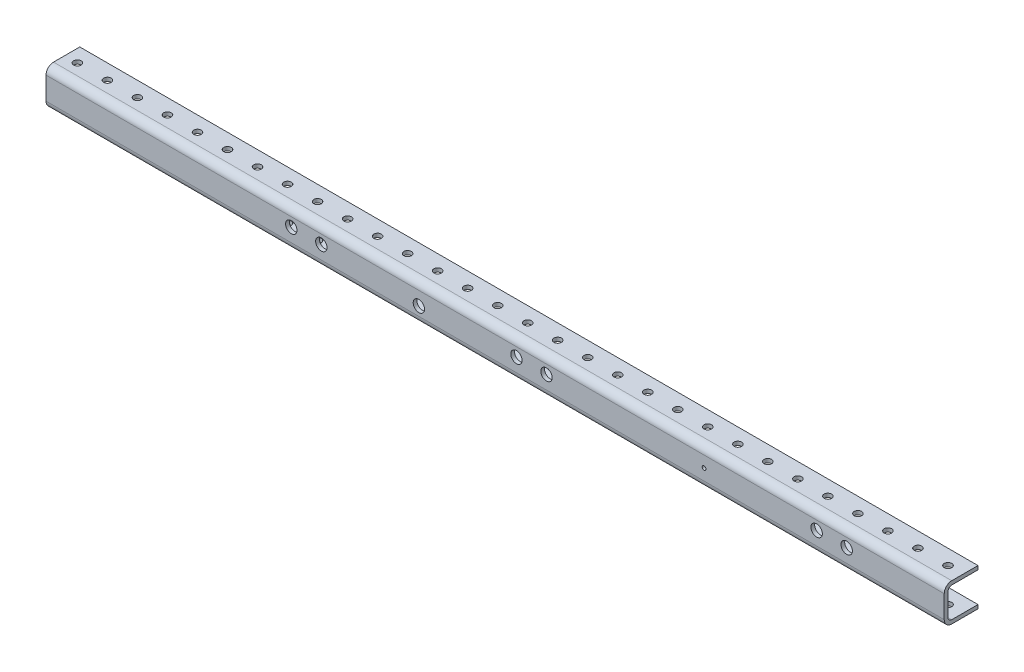
SolidWorks part; units mm, degrees
material "5052-O, Rod (SS)"
ref_plane "Front Plane" through (0, 0, 0) normal (0, 0, 1) x (1, 0, 0)
ref_plane "Top Plane" through (0, 0, 0) normal (0, 1, 0) x (1, 0, 0)
ref_plane "Right Plane" through (0, 0, 0) normal (1, 0, 0) x (0, 0, -1)
ref_plane "Plane1" through (0, 0, 3.175) normal (0, 0, 1) x (1, 0, 0)
sketch "Sketch1" plane through (0, 0, 3.175) normal (0, 0, 1) x (1, 0, 0)
  line L0 (872.98, -7.202) -> (872.98, 24.548)
  line L1 (872.98, 24.548) -> (-16.02, 24.548)
  line L2 (-16.02, 24.548) -> (-16.02, -7.202)
  line L3 (-16.02, -7.202) -> (872.98, -7.202)
extrude "Extrude1" add sketch "Sketch1" against normal blind 28.575
sketch "Sketch2" plane through (-16.02, 0, 0) normal (-1, 0, 0) x (0, 0, 1)
  line L0 (-25.4, 21.373) -> (-25.4, -4.027)
  line L1 (-25.4, -4.027) -> (0, -4.027)
  line L2 (0, -4.027) -> (0, 21.373)
  line L3 (0, 21.373) -> (-25.4, 21.373)
extrude "Extrude2" cut sketch "Sketch2" against normal up to next
hole_wizard "Hole1" positions "Sketch4" profile "Sketch3" legacy
sketch "Sketch4" plane through (0, 24.548, 0) normal (0, 1, 0) x (-1, 0, 0)
  point P0 (3.32, -12.7)
sketch "Sketch3" plane through (-3.32, 24.548, -12.7) normal (1, 0, 0) x (0, 0, 1)
  line L0 (0, 0) -> (0, 3.175)
  line L1 (0, 3.175) -> (3.175, 3.175)
  line L2 (3.175, 3.175) -> (3.175, 0)
  line L3 (3.175, 0) -> (0, 0)
  line L4 (0, 110) -> (0, -10) construction
  dimension "Diameter" = 6.35
  dimension "Depth" = 3.175
sketch3d "3DSketch1"
  point P0 (428.6664, 8.6668, -7.2024)
  point P1 (528.6664, 8.6668, -7.2024)
ref_axis "Axis1" through (528.6664, 8.6668, -7.2024) along (-1, 0, 0)
pattern_linear "LPattern1" count 35 spacing 25.4 along (1, 0, 0) of "Hole1"
hole_wizard "Hole2" positions "Sketch6" profile "Sketch5" legacy
sketch "Sketch6" plane through (0, 0, 3.175) normal (0, 0, 1) x (1, 0, 0)
  point P0 (66.53, 10.578)
sketch "Sketch5" plane through (66.53, 10.578, 3.175) normal (1, 0, 0) x (0, -1, 0)
  line L0 (0, 0) -> (0, 3.175)
  line L1 (0, 3.175) -> (4.826, 3.175)
  line L2 (4.826, 3.175) -> (4.826, 0)
  line L3 (4.826, 0) -> (0, 0)
  line L4 (0, 110) -> (0, -10) construction
  dimension "Diameter" = 9.652
  dimension "Depth" = 3.175
sketch3d "3DSketch2"
  point P0 (428.8468, 8.4517, -7.1294)
  point P1 (528.8468, 8.4517, -7.1294)
ref_axis "Axis2" through (528.8468, 8.4517, -7.1294) along (-1, 0, 0)
pattern_linear "LPattern2" count 12 spacing 25.4 along (1, 0, 0) skipping (2, 0), (3, 0), (4, 0), (5, 0), (6, 0), (7, 0), (8, 0), (9, 0) of "Hole2"
hole_wizard "Hole3" positions "Sketch8" profile "Sketch7" legacy
sketch "Sketch8" plane through (0, 0, 3.175) normal (0, 0, 1) x (1, 0, 0)
  point P0 (428.48, 6.768)
sketch "Sketch7" plane through (428.48, 6.768, 3.175) normal (1, 0, 0) x (0, -1, 0)
  line L0 (0, 0) -> (0, 3.175)
  line L1 (0, 3.175) -> (4.826, 3.175)
  line L2 (4.826, 3.175) -> (4.826, 0)
  line L3 (4.826, 0) -> (0, 0)
  line L4 (0, 110) -> (0, -10) construction
  dimension "Diameter" = 9.652
  dimension "Depth" = 3.175
hole_wizard "Hole4" positions "Sketch10" profile "Sketch9" legacy
sketch "Sketch10" plane through (0, 0, 3.175) normal (0, 0, 1) x (1, 0, 0)
  point P0 (511.03, 10.578)
sketch "Sketch9" plane through (511.03, 10.578, 3.175) normal (1, 0, 0) x (0, -1, 0)
  line L0 (0, 0) -> (0, 3.175)
  line L1 (0, 3.175) -> (4.826, 3.175)
  line L2 (4.826, 3.175) -> (4.826, 0)
  line L3 (4.826, 0) -> (0, 0)
  line L4 (0, 110) -> (0, -10) construction
  dimension "Diameter" = 9.652
  dimension "Depth" = 3.175
sketch3d "3DSketch3"
  point P0 (429.3014, 8.4448, -7.1738)
  point P1 (529.3014, 8.4448, -7.1738)
ref_axis "Axis3" through (529.3014, 8.4448, -7.1738) along (-1, 0, 0)
pattern_linear "LPattern3" count 12 spacing 25.4 along (1, 0, 0) skipping (2, 0), (3, 0), (4, 0), (5, 0), (6, 0), (7, 0), (8, 0), (9, 0) of "Hole4"
hole_wizard "Hole5" positions "Sketch12" profile "Sketch11" legacy
sketch "Sketch12" plane through (0, 0, 3.175) normal (0, 0, 1) x (1, 0, 0)
  point P0 (669.78, 8.673)
sketch "Sketch11" plane through (669.78, 8.673, 3.175) normal (1, 0, 0) x (0, -1, 0)
  line L0 (0, 0) -> (0, 3.175)
  line L1 (0, 3.175) -> (1.5875, 3.175)
  line L2 (1.5875, 3.175) -> (1.5875, 0)
  line L3 (1.5875, 0) -> (0, 0)
  line L4 (0, 110) -> (0, -10) construction
  dimension "Diameter" = 3.175
  dimension "Depth" = 3.175
hole_wizard "Hole6" positions "Sketch14" profile "Sketch13" legacy
sketch "Sketch14" plane through (0, -4.027, 0) normal (0, 1, 0) x (-1, 0, 0)
  point P0 (3.32, -12.7)
sketch "Sketch13" plane through (-3.32, -4.027, -12.7) normal (1, 0, 0) x (0, 0, 1)
  line L0 (0, 0) -> (0, 3.175)
  line L1 (0, 3.175) -> (3.175, 3.175)
  line L2 (3.175, 3.175) -> (3.175, 0)
  line L3 (3.175, 0) -> (0, 0)
  line L4 (0, 110) -> (0, -10) construction
  dimension "Diameter" = 6.35
  dimension "Depth" = 3.175
sketch3d "3DSketch4"
  point P0 (428.6444, 8.4444, -7.1991)
  point P1 (528.6444, 8.4444, -7.1991)
ref_axis "Axis4" through (528.6444, 8.4444, -7.1991) along (-1, 0, 0)
pattern_linear "LPattern4" count 35 spacing 25.4 along (1, 0, 0) of "Hole6"
fillet "Fillet1" radius 3.175 1 edges at (428.48, 21.373, 0) tangent propagation no
fillet "Fillet2" radius 3.175 1 edges at (428.48, -4.027, 0) tangent propagation no
fillet "Fillet3" radius 6.35 1 edges at (428.48, -7.202, 3.175) tangent propagation no
fillet "Fillet4" radius 6.35 1 edges at (428.48, 24.548, 3.175) tangent propagation no
ref_plane "Plane2" through (872.98, 24.548, -3.175) normal (1, 0, 0) x (0, 0, -1)
sketch "Sketch16" plane through (0, 24.548, 0) normal (0, 1, 0) x (1, 0, 0)
  line L0 (112.98, 3.175) -> (112.98, 25.4) construction
  line L1 (-16.02, 3.175) -> (872.98, 3.175) construction
  line L2 (872.98, 25.4) -> (-16.02, 25.4) construction
  line L3 (872.98, 25.4) -> (872.98, 3.175) construction
  line L6 (112.98, 3.175) -> (112.98, 25.4)
  line L7 (112.98, 25.4) -> (-16.02, 25.4)
  line L9 (112.98, 25.4) -> (-32.7801, 25.4)
  line L10 (112.98, 25.4) -> (112.98, -46.1048)
  line L11 (112.98, -46.1048) -> (-32.7801, -46.1048)
  line L12 (-32.7801, 25.4) -> (-32.7801, -46.1048)
  dimension "D1" = 760
extrude "Cut-Extrude2" cut sketch "Sketch16" against normal blind 75 contours L10 L11 L12 L9
